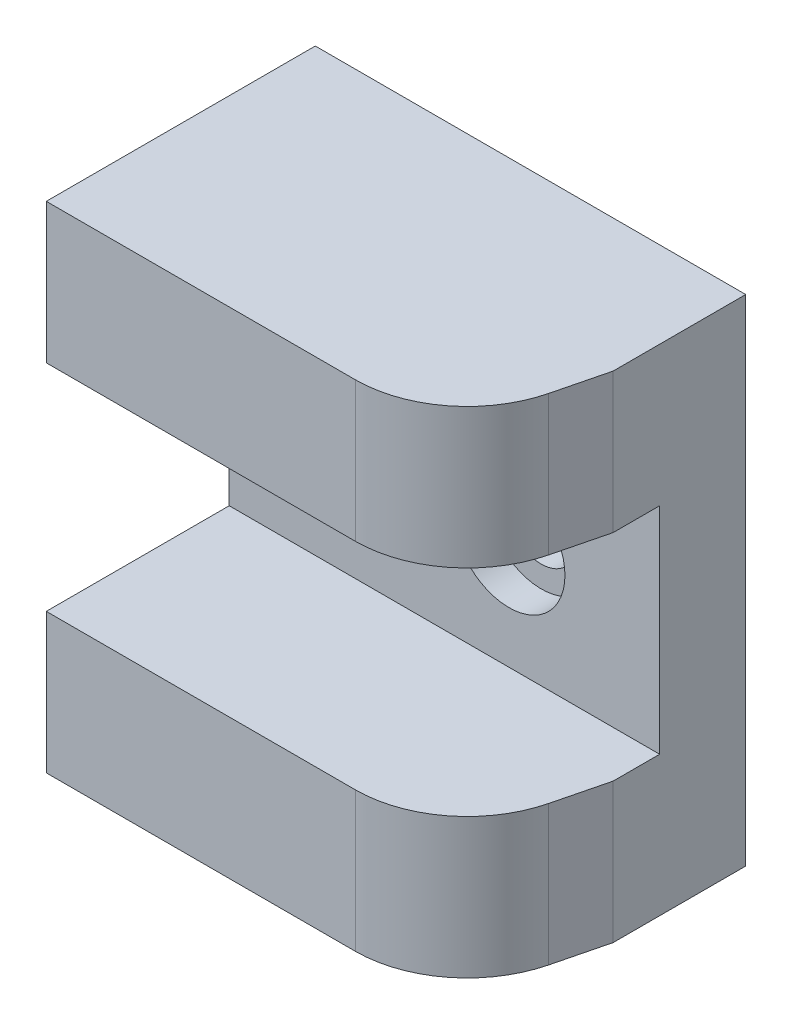
SolidWorks part; units mm, degrees
ref_plane "前视基准面" through (0, 0, 0) normal (0, 0, 1) x (1, 0, 0)
ref_plane "上视基准面" through (0, 0, 0) normal (0, 1, 0) x (1, 0, 0)
ref_plane "右视基准面" through (0, 0, 0) normal (1, 0, 0) x (0, 0, -1)
sketch "草图1" plane through (0, 0, 0) normal (0, 0, 1) x (1, 0, 0)
  line L0 (130, 105) -> (130, -105) construction
  line L1 (130, 82) -> (110, 82)
  line L2 (130, 82) -> (130, 105)
  line L4 (110, 82) -> (110, 105)
  line L5 (75, 105) -> (130, 105) construction
  line L6 (130, 105) -> (110, 105)
  dimension "D1" = 20
  dimension "D2" = 23
extrude "凸台-拉伸1" add sketch "草图1" along normal blind 12.5
sketch "草图2" plane through (0, 105, 0) normal (0, 1, 0) x (1, 0, 0)
  line L6 (129.4025, -8.558) -> (130, -6.1617)
  line L8 (130, -6.1617) -> (130, -12.5)
  line L10 (130, -12.5) -> (124.357, -12.5)
  arc A1 (124.357, -12.5) -> (129.4025, -8.558) centre (124.357, -7.3) ccw
extrude "切除-拉伸1" cut sketch "草图2" against normal blind 26.5
sketch "草图3" plane through (0, 0, 12.5) normal (0, 0, 1) x (1, 0, 0)
  line L0 (110, 93.5) -> (130, 93.5) construction
  line L1 (110, 105) -> (110, 82) construction
  line L4 (110, 98.5) -> (130, 98.5)
  line L5 (110, 98.5) -> (110, 88.5)
  line L6 (110, 88.5) -> (130, 88.5)
  line L7 (130, 98.5) -> (130, 88.5)
  line L8 (110, 98.5) -> (130, 88.5) construction
  line L9 (110, 88.5) -> (130, 98.5) construction
  point P6 (120, 93.5)
  dimension "D1" = 10
  dimension "D2" = 20
extrude "切除-拉伸2" cut sketch "草图3" against normal blind 8.5
sketch "草图4" plane through (0, 0, 4) normal (0, 0, 1) x (1, 0, 0)
  line L0 (110, 93.5) -> (130, 93.5) construction
  line L1 (110, 98.5) -> (110, 88.5) construction
  line L3 (130, 88.5) -> (130, 98.5) construction
  circle A0 centre (115, 93.5) radius 1.5
  circle A2 centre (123, 93.5) radius 1.5
  dimension "D1" = 3
  dimension "D2" = 8
  dimension "D3" = 5
hole_wizard "M3 六角头螺栓的柱形沉头孔1" positions "草图7" profile "草图8" counterbore size "M3" standard "GB" end condition through all
sketch "草图7" plane through (0, 0, 4) normal (0, 0, 1) x (1, 0, 0)
  point P0 (115, 93.5)
  point P3 (123, 93.5)
sketch "草图8" plane through (115, 93.5, 4) normal (1, 0, 0) x (0, -1, 0)
  line L0 (0, 0) -> (0, 4)
  line L1 (0, 4) -> (1.6, 4)
  line L3 (1.6, 4) -> (1.6, 1.5)
  line L4 (1.6, 1.5) -> (2.6, 1.5)
  line L5 (2.6, 1.5) -> (2.6, 0)
  line L7 (2.6, 0) -> (0, 0)
  line L11 (0, -6.35) -> (0, 107.95) construction
  dimension "通孔孔直径" = 3.2
  dimension "通孔孔深度" = 4
  dimension "柱形沉头孔直径" = 5.2
  dimension "柱形沉头孔深度" = 1.5
move or copy body "实体-移动/复制1" [suppressed] bodies to move or copy 109
